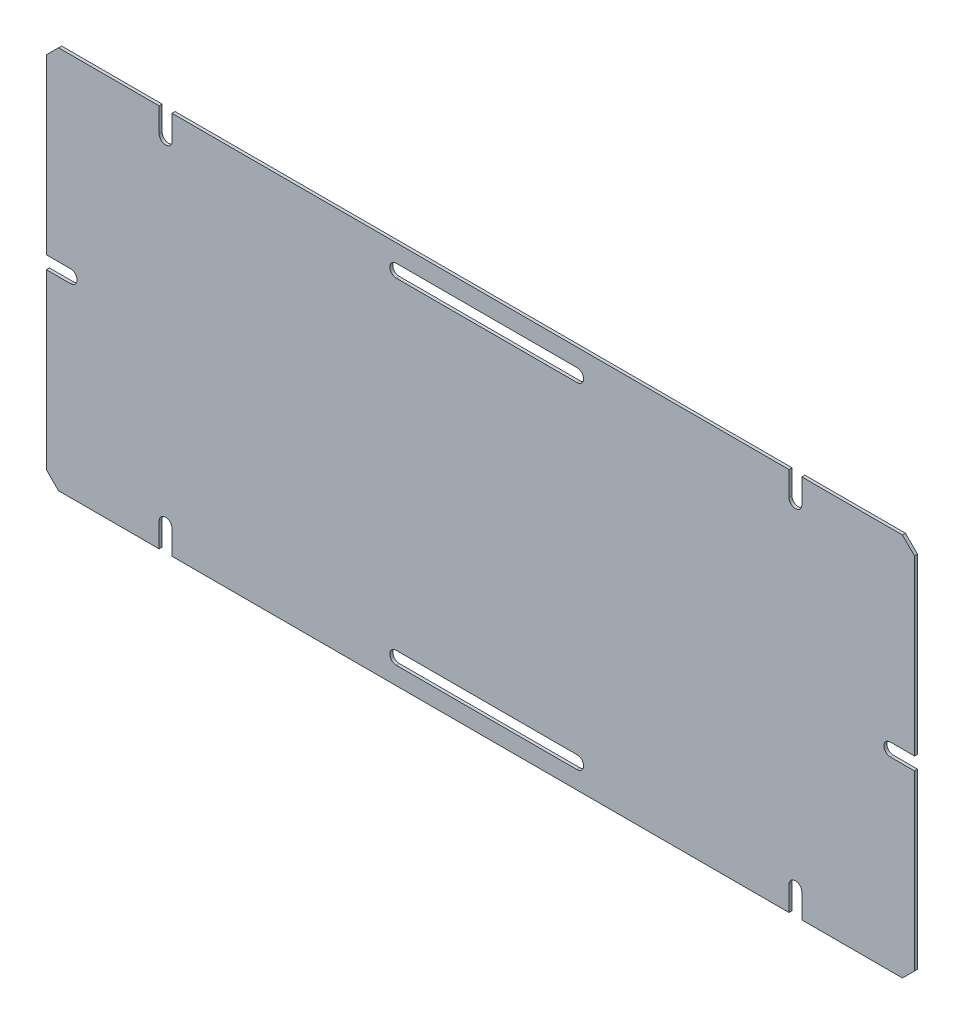
SolidWorks part; units mm, degrees
material "PE High Density"
ref_plane "Front" through (0, 0, 0) normal (0, 0, 1) x (1, 0, 0)
ref_plane "Top" through (0, 0, 0) normal (0, 1, 0) x (1, 0, 0)
ref_plane "Right" through (0, 0, 0) normal (1, 0, 0) x (0, 0, -1)
ref_axis "Axis1" through (0, 0, 55) along (0, 0, -1)
sketch "Sketch1" plane through (0, 0, 0) normal (0, 0, 1) x (1, 0, 0)
  line L1 (-227.584, 100.584) -> (227.584, 100.584)
  line L2 (-227.584, 100.584) -> (-227.584, -100.584)
  line L3 (-227.584, -100.584) -> (227.584, -100.584)
  line L4 (227.584, 100.584) -> (227.584, -100.584)
  line L5 (-227.584, 100.584) -> (227.584, -100.584) construction
  line L6 (-227.584, -100.584) -> (227.584, 100.584) construction
  point P0 (0, 0)
  dimension "D1" = 201.168
  dimension "D2" = 455.168
extrude "Boss-Extrude1" add sketch "Sketch1" along normal blind 1.5875
hole_wizard "1/4 Clearance Hole1" positions "Sketch2" profile "Sketch3" hole size "1/4" standard "ANSI Inch" end condition up to next
sketch "Sketch2" plane through (0, 0, 1.5875) normal (0, 0, 1) x (1, 0, 0)
  line L2 (-214.884, 87.884) -> (214.884, 87.884) construction
  line L3 (-214.884, 87.884) -> (-214.884, -87.884) construction
  line L4 (-214.884, -87.884) -> (214.884, -87.884) construction
  line L5 (214.884, 87.884) -> (214.884, -87.884) construction
  line L6 (-214.884, 87.884) -> (214.884, -87.884) construction
  line L7 (-214.884, -87.884) -> (214.884, 87.884) construction
  line L8 (-227.584, 100.584) -> (-227.584, -100.584) construction
  line L9 (227.584, 100.584) -> (-227.584, 100.584) construction
  line L10 (-227.584, -100.584) -> (227.584, -100.584) construction
  line L11 (227.584, -100.584) -> (227.584, 100.584) construction
  line L12 (-214.884, 0) -> (214.884, 0) construction
  line L14 (0, 87.884) -> (0, -87.884) construction
  line L15 (-165.1, 87.884) -> (-165.1, -87.884) construction
  line L17 (165.1, 87.884) -> (165.1, -87.884) construction
  point P0 (-165.1, 87.884)
  point P2 (165.1, 87.884)
  point P4 (214.884, 0)
  point P6 (-214.884, 0)
  point P8 (-165.1, -87.884)
  point P10 (165.1, -87.884)
  point P224 (214.884, 0)
  dimension "D1" = 12.7
  dimension "D2" = 12.7
  dimension "D3" = 12.7
  dimension "D4" = 12.7
  dimension "D5" = 330.2
sketch "Sketch3" plane through (-165.1, 87.884, 1.5875) normal (1, 0, 0) x (0, -1, 0)
  line L0 (0, 0) -> (0, 1.5875)
  line L1 (0, 1.5875) -> (3.3782, 1.5875)
  line L2 (3.3782, 1.5875) -> (3.3782, 0)
  line L5 (3.3782, 0) -> (0, 0)
  line L11 (0, -6.35) -> (0, 107.95) construction
  dimension "Thru Hole Dia." = 6.7564
  dimension "Thru Hole Depth" = 1.5875
hole_wizard "1/4 Clearance Slot1" positions "Sketch4" profile "Sketch5" size "1/4" standard "ANSI Inch" slot yes end condition up to next
sketch "Sketch4" plane through (0, 0, 1.5875) normal (0, 0, 1) x (1, 0, 0)
  line L0 (-47.5488, -87.884) -> (54.0512, -87.884) construction
  line L1 (3.2512, 87.884) -> (3.2512, -87.884) construction
  line L3 (227.584, 100.584) -> (-227.584, 100.584) construction
  line L4 (227.584, -100.584) -> (227.584, 100.584) construction
  point P0 (3.2512, -87.884)
  point P4 (3.2512, 87.884)
  dimension "D1" = 101.6
  dimension "D2" = 12.7
  dimension "D3" = 175.768
  dimension "D4" = 224.3328
sketch "Sketch5" plane through (3.2512, -87.884, 1.5875) normal (1, 0, 0) x (0, -1, 0)
  line L0 (0, 0) -> (0, 1.5875)
  line L1 (0, 1.5875) -> (3.3782, 1.5875)
  line L2 (3.3782, 1.5875) -> (3.3782, 0)
  line L5 (3.3782, 0) -> (0, 0)
  line L11 (0, -6.35) -> (0, 107.95) construction
  dimension "Thru Hole Dia." = 6.7564
  dimension "Thru Hole Depth" = 1.5875
sketch "Sketch6" plane through (0, 0, 1.5875) normal (0, 0, 1) x (1, 0, 0)
  line L0 (165.1, 91.2622) -> (165.1, 84.5058) construction
  line L1 (-168.4782, 87.884) -> (-161.7218, 87.884)
  line L2 (-168.4782, 87.884) -> (-168.4782, 102.362)
  line L3 (-168.4782, 102.362) -> (-161.7218, 102.362)
  line L4 (-161.7218, 87.884) -> (-161.7218, 102.362)
  line L5 (-168.4782, 87.884) -> (-161.7218, 102.362) construction
  line L6 (-168.4782, 102.362) -> (-161.7218, 87.884) construction
  line L7 (161.7218, 87.884) -> (168.4782, 87.884)
  line L8 (161.7218, 87.884) -> (161.7218, 102.362)
  line L9 (161.7218, 102.362) -> (168.4782, 102.362)
  line L10 (168.4782, 87.884) -> (168.4782, 102.362)
  line L11 (161.7218, 87.884) -> (168.4782, 102.362) construction
  line L12 (161.7218, 102.362) -> (168.4782, 87.884) construction
  line L13 (-165.1, 91.2622) -> (-165.1, 84.5058) construction
  circle A0 centre (-165.1, 87.884) radius 3.3782 construction
  circle A1 centre (165.1, 87.884) radius 3.3782 construction
  point P4 (-165.1, 95.123)
  point P11 (165.1, 95.123)
  point P17 (165.1, 87.884)
  point P18 (-165.1, 87.884)
  point P19 (165.1, 87.884)
  point P23 (-165.1, 87.884)
  dimension "D1" = 14.478
chamfer "Chamfer1" distance 6.35 angle 45 4 edges at (-227.584, -100.584, 0.7937) (-227.584, 100.584, 0.7937) (227.584, -100.584, 0.7937) (227.584, 100.584, 0.7937)
extrude "Cut-Extrude1" cut sketch "Sketch6" against normal up to next
mirror "Mirror1" about plane through (0, 0, 0) normal (0, 1, 0) of "Cut-Extrude1"
sketch "Sketch7" plane through (0, 0, 1.5875) normal (0, 0, 1) x (1, 0, 0)
  line L0 (-214.884, 3.3782) -> (-214.884, -3.3782) construction
  line L2 (-214.884, 3.3782) -> (-229.362, 3.3782)
  line L3 (-214.884, 3.3782) -> (-214.884, -3.3782)
  line L4 (-214.884, -3.3782) -> (-229.362, -3.3782)
  line L5 (-229.362, 3.3782) -> (-229.362, -3.3782)
  line L6 (-214.884, 3.3782) -> (-229.362, -3.3782) construction
  line L7 (-214.884, -3.3782) -> (-229.362, 3.3782) construction
  circle A0 centre (-214.884, 0) radius 3.3782 construction
  point P8 (-222.123, 0)
  point P9 (0, 0)
  dimension "D1" = 14.478
extrude "Cut-Extrude2" cut sketch "Sketch7" against normal up to next
mirror "Mirror2" about plane through (0, 0, 0) normal (1, 0, 0) of "Cut-Extrude2"
